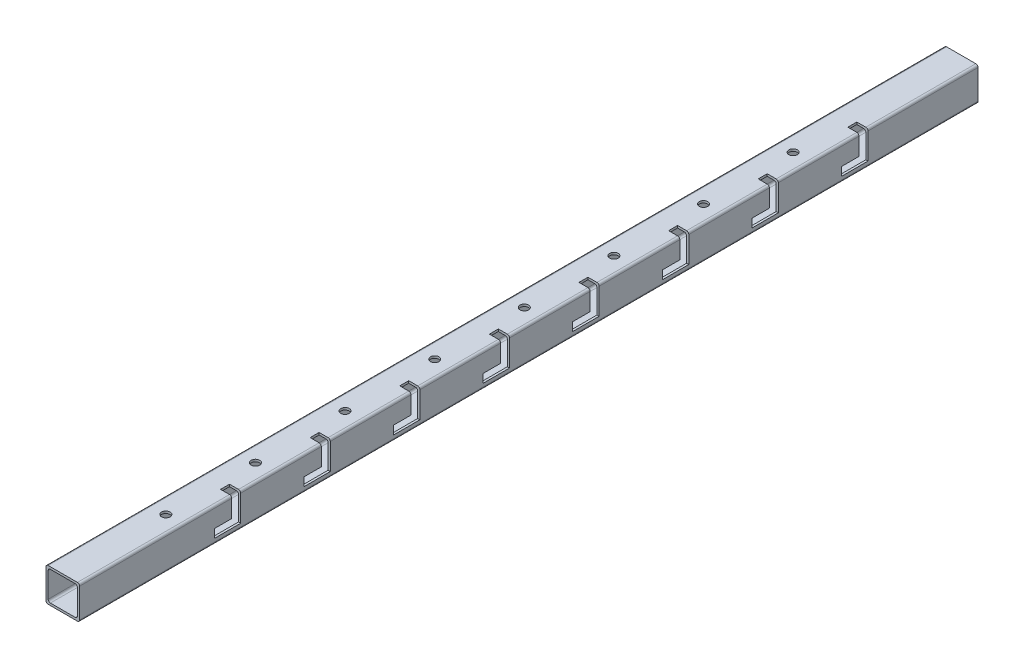
SolidWorks part; units mm, degrees
ref_plane "Front Plane" through (0, 0, 0) normal (0, 0, 1) x (1, 0, 0)
ref_plane "Top Plane" through (0, 0, 0) normal (0, 1, 0) x (1, 0, 0)
ref_plane "Right Plane" through (0, 0, 0) normal (1, 0, 0) x (0, 0, -1)
sketch "Sketch1" plane through (0, 0, 0) normal (0, 0, 1) x (1, 0, 0)
  line L0 (-9.525, 0) -> (9.525, 0) construction
  line L1 (0, -9.525) -> (0, 9.525) construction
  line L2 (8.2804, 0) -> (8.2804, 8.2804) construction
  line L3 (-9.525, -9.525) -> (9.525, -9.525) construction
  line L4 (-9.525, -9.525) -> (-9.525, 9.525) construction
  line L5 (-9.525, 9.525) -> (9.525, 9.525) construction
  line L6 (9.525, -9.525) -> (9.525, 9.525) construction
  line L7 (-9.525, -9.525) -> (9.525, 9.525) construction
  line L8 (-9.525, 9.525) -> (9.525, -9.525) construction
  line L9 (8.2804, 8.2804) -> (-8.2804, 8.2804) construction
  line L10 (-8.2804, 8.2804) -> (-8.2804, -8.2804) construction
  line L11 (-8.2804, -8.2804) -> (8.2804, -8.2804) construction
  line L12 (8.2804, -8.2804) -> (8.2804, 0) construction
  point P0 (0, 0)
  point P4 (0, 0)
  point P9 (0, 0)
  point P10 (8.2804, 0)
  point P13 (0, -8.2804)
  point P14 (-8.2804, 0)
  point P15 (0, 8.2804)
  dimension "Width" = 19.05
  dimension "Wall Thickness" = 1.2446
  dimension "Height" = 19.05
  dimension "D1" = 1.2446
  dimension "D2" = 1.2446
  dimension "D3" = 1.2446
sketch "Sketch2" plane through (0, 0, 0) normal (1, 0, 0) x (0, 0, -1)
  line L0 (254.635, 9.525) -> (-254.635, 9.525) construction
  point P3 (-232.7275, 9.525)
  point P5 (232.7275, 9.525)
  point P7 (0, 9.525)
  dimension "D1" = 21.9075
  dimension "D2" = 21.9075
  dimension "Length" = 509.27
sketch "Sketch3" plane through (0, 0, 0) normal (0, 0, 1) x (1, 0, 0)
  line L1 (9.525, 9.525) -> (-9.525, 9.525)
  line L2 (-9.525, 9.525) -> (-9.525, -9.525)
  line L3 (-9.525, -9.525) -> (9.525, -9.525) construction
  line L4 (-9.525, -9.525) -> (9.525, -9.525)
  line L5 (9.525, -9.525) -> (9.525, 9.525)
  line L6 (-8.2804, 8.2804) -> (8.2804, 8.2804)
  line L7 (8.2804, 8.2804) -> (8.2804, -8.2804)
  line L8 (8.2804, -8.2804) -> (-8.2804, -8.2804)
  line L9 (-8.2804, -8.2804) -> (-8.2804, 8.2804)
extrude "Boss-Extrude1" add sketch "Sketch3" along normal mid plane 509.27
fillet "Fillet1" radius 1.2446 8 edges at (-9.525, 9.525, 0) (8.2804, -8.2804, 0) (-8.2804, -8.2804, 0) (-8.2804, 8.2804, 0) (8.2804, 8.2804, 0) (9.525, -9.525, 0) (-9.525, -9.525, 0) (9.525, 9.525, 0)
sketch "Sketch4" plane through (0, 9.525, 0) normal (0, 1, 0) x (1, 0, 0)
  line L0 (0, 254.635) -> (0, 159.385) construction
  line L1 (8.2804, 254.635) -> (-8.2804, 254.635) construction
  line L2 (0, 159.385) -> (0, 108.585) construction
  circle A0 centre (0, 159.385) radius 2.413
  circle A1 centre (0, 108.585) radius 2.413
  circle A2 centre (0, 57.785) radius 2.413
  circle A3 centre (0, 6.985) radius 2.413
  circle A4 centre (0, -43.815) radius 2.413
  circle A5 centre (0, -94.615) radius 2.413
  circle A6 centre (0, -145.415) radius 2.413
  circle A7 centre (0, -196.215) radius 2.413
  dimension "D2" = 4.826
  dimension "D4" = 4.826
  dimension "D1" = 95.25
  dimension "D3" = 50.8
  dimension "D5" = 7
extrude "Cut-Extrude1" cut sketch "Sketch4" against normal through all
sketch "Sketch6" plane through (-9.525, 0, 0) normal (-1, 0, 0) x (0, 0, 1)
  line L0 (-254.635, 0) -> (-179.705, 0) construction
  line L1 (-254.635, 8.2804) -> (-254.635, -8.2804) construction
  line L2 (-182.118, -1.651) -> (-187.198, -1.651)
  line L7 (-182.118, -6.477) -> (-177.292, -1.651) construction
  line L12 (-177.292, -6.477) -> (-182.118, -6.477)
  line L13 (-177.292, -6.477) -> (-177.292, -1.651)
  line L14 (-177.292, -1.651) -> (-182.118, -1.651)
  line L15 (-182.118, -6.477) -> (-182.118, -1.651) construction
  line L16 (-192.278, 9.525) -> (-192.278, -6.477)
  line L17 (-177.292, -6.477) -> (-182.118, -1.651) construction
  line L18 (-254.635, 9.525) -> (254.635, 9.525) construction
  line L19 (-192.278, -6.477) -> (-182.118, -6.477)
  line L20 (-187.198, -1.651) -> (-187.198, 9.525)
  line L21 (-187.198, 9.525) -> (-192.278, 9.525)
  point P12 (-179.705, -4.064)
  dimension "D1" = 74.93
  dimension "D2" = 16.002
  dimension "D3" = 4.826
  dimension "D4" = 4.826
  dimension "D5" = 10.16
  dimension "D6" = 5.08
extrude "Cut-Extrude3" cut sketch "Sketch6" along normal blind 6.35 from surface starting at face at (9.525, 0, 0)
pattern_linear "LPattern2" count 8 spacing 50.8 along (0, 0, 1) of "Cut-Extrude3"
equation "\"D1@Boss-Extrude1\" = \"Length@Sketch2\""
equation "\"D1@Sketch2\" = \"Width@Sketch1\" * 1.15"
equation "\"D2@Sketch2\"=\"D1@Sketch2\""
equation "\"D1@Sketch1\"=\"Wall Thickness@Sketch1\""
equation "\"D2@Sketch1\"=\"Wall Thickness@Sketch1\""
equation "\"D3@Sketch1\"=\"Wall Thickness@Sketch1\""
equation "\"D1@Fillet1\"=\"Wall Thickness@Sketch1\""
